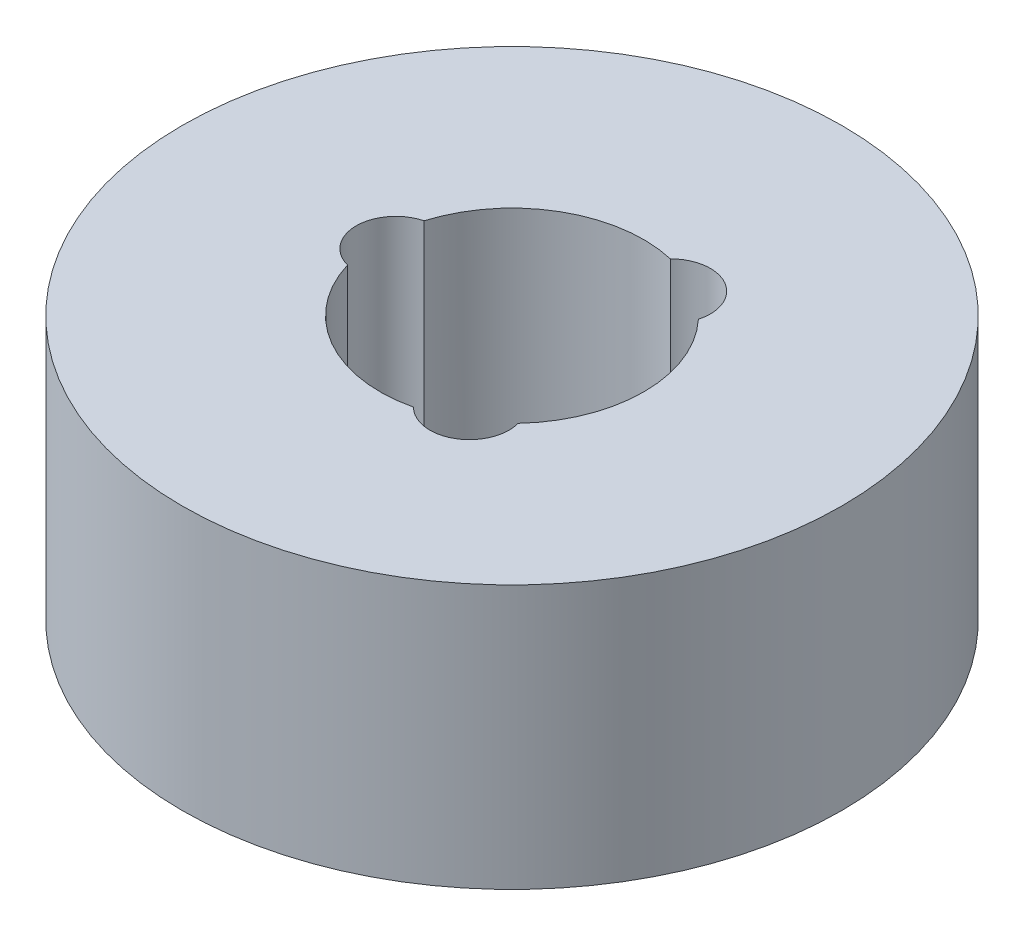
SolidWorks part; units mm, degrees
ref_plane "Front Plane" through (0, 0, 0) normal (0, 0, 1) x (1, 0, 0)
ref_plane "Top Plane" through (0, 0, 0) normal (0, 1, 0) x (1, 0, 0)
ref_plane "Right Plane" through (0, 0, 0) normal (1, 0, 0) x (0, 0, -1)
sketch "Sketch1" plane through (0, 0, 0) normal (0, 1, 0) x (1, 0, 0)
  circle A0 centre (0, 0) radius 12.5
  dimension "FLANGE_OD" = 25
extrude "Boss-Extrude1" add sketch "Sketch1" along normal blind 10
sketch "Sketch2" plane through (0, 0, 0) normal (0, 1, 0) x (1, 0, 0)
  circle A0 centre (0, 0) radius 5
  dimension "BORE_D" = 10
extrude "Cut-Extrude1" cut sketch "Sketch2" along normal through all
sketch "Sketch3" plane through (0, 10, 0) normal (0, 1, 0) x (1, 0, 0)
  circle A0 centre (0, 0) radius 4.4062 construction
  circle A1 centre (-4.4062, 0) radius 1.5
  dimension "BOLT_D" = 3
  dimension "BOLT_PCD" = 8.8123
extrude "Cut-Extrude2" cut sketch "Sketch3" against normal blind 8.5554
pattern_circular "CirPattern1" count 3 over 360 about axis through (0, 0, 0) along (0, 1, 0) of "Cut-Extrude2"
